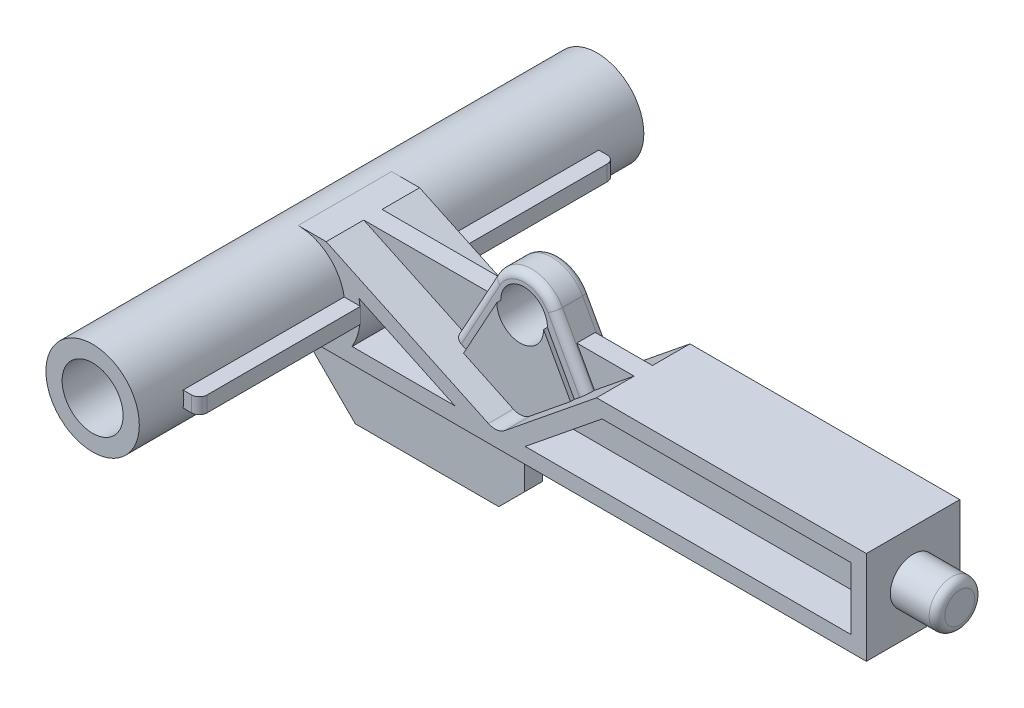
SolidWorks part; units mm, degrees
ref_plane "Front Plane" through (0, 0, 0) normal (0, 0, 1) x (1, 0, 0)
ref_plane "Top Plane" through (0, 0, 0) normal (0, 1, 0) x (1, 0, 0)
ref_plane "Right Plane" through (0, 0, 0) normal (1, 0, 0) x (0, 0, -1)
sketch "Sketch1" plane through (0, 0, 0) normal (0, 0, 1) x (1, 0, 0)
  line L0 (0, 0) -> (36.5, 0)
  line L1 (36.5, 0) -> (36.5, 6)
  line L2 (36.5, 6) -> (20.75, 6)
  line L3 (20.75, 6) -> (11.75, 6) construction
  line L4 (20.75, 6) -> (20.75, 2) construction
  line L5 (20.75, 2) -> (11.75, 2) construction
  line L6 (11.75, 2) -> (11.75, 6) construction
  line L7 (16.75, 10) -> (16.75, 2) construction
  line L8 (12.75, 6) -> (20.75, 6) construction
  line L9 (15.5737, 2.9411) -> (11.75, 6)
  line L10 (11.75, 6) -> (0, 6)
  line L11 (0, 6) -> (0, 0) construction
  arc A1 (20.75, 6) -> (19.541, 3.1347) centre (16.75, 6) cw
  arc A2 (15.5737, 2.9411) -> (19.541, 3.1347) centre (17.4478, 5.2837) ccw
  circle A4 centre (0, 3) radius 3
  dimension "D4" = 3
  dimension "D1" = 36.5
  dimension "D2" = 6
  dimension "D3" = 15.75
  dimension "D5" = 4
  dimension "D6" = 9
extrude "Boss-Extrude3" add sketch "Sketch1" along normal mid plane 6 contours A4 L0 L1 L2 A1 A2 L9 L10 region at (19.7193, 2.8172, 0)
sketch "Sketch2" plane through (0, 0, 0) normal (0, 0, 1) x (1, 0, 0)
  circle A0 centre (0, 3) radius 3
extrude "Boss-Extrude4" add sketch "Sketch2" along normal mid plane 32.41
sketch "Sketch5" plane through (0, 0, 16.205) normal (0, 0, 1) x (1, 0, 0)
  circle A0 centre (0, 3) radius 1.96
  dimension "D1" = 3.92
extrude "Cut-Extrude2" cut sketch "Sketch5" against normal blind 32.8
sketch "Sketch6" plane through (36.5, 0, 0) normal (1, 0, 0) x (0, 0, -1)
  circle A0 centre (0, 3) radius 1.465
  dimension "D1" = 2.93
extrude "Boss-Extrude7" add sketch "Sketch6" along normal blind 3 contours A0
fillet "Fillet1" radius 0.5 1 edges at (39.5, 3, -1.465)
sketch "Sketch12" plane through (0, 0, 0) normal (0, 0, 1) x (1, 0, 0)
  line L0 (36.5, 0) -> (12.12, 0) construction
  line L1 (0, 0) -> (36.5, 0) construction
  line L2 (12.12, 0) -> (12.12, -3.97)
  line L3 (12.12, -3.97) -> (10.4795, -5.6105)
  line L4 (10.4795, -5.6105) -> (1.2595, -5.6105)
  line L5 (1.2595, -5.6105) -> (-2.8064, -1.5446)
  line L6 (-2.8064, -1.5446) -> (-2.8064, 1.9396)
  line L7 (12.12, 0) -> (0, 0)
  circle A0 centre (0, 3) radius 3 construction
  arc A1 (-2.8064, 1.9396) -> (0, 0) centre (0, 3) ccw
  dimension "D1" = 24.38
  dimension "D2" = 3.97
  dimension "D3" = 2.32
  dimension "D4" = 9.22
  dimension "D5" = 5.75
extrude "Boss-Extrude8" add sketch "Sketch12" along normal mid plane 1.18
sketch "Sketch14" plane through (0, 0, 0) normal (0, 0, 1) x (1, 0, 0)
  line L1 (4, 2.5) -> (4, 3.5)
  line L2 (4, 3.5) -> (2.958, 3.5)
  line L3 (4, 2.5) -> (2.958, 2.5)
  circle A0 centre (0, 3) radius 3 construction
  arc A2 (2.958, 3.5) -> (2.958, 2.5) centre (0, 3) cw
  point P6 (4, 3)
  dimension "D1" = 1
extrude "Boss-Extrude9" add sketch "Sketch14" along normal mid plane 26.7
fillet "Fillet7" radius 0.5 1 edges at (4, 3, 13.35)
fillet "Fillet8" radius 0.5 1 edges at (4, 3, -13.35)
sketch "Sketch15" plane through (0, 0, 0) normal (0, 0, 1) x (1, 0, 0)
  line L0 (5.875, 6) -> (27.0772, 6)
  line L1 (11.75, 6) -> (0, 6) construction
  line L2 (36.5, 6) -> (20.75, 6) construction
  line L3 (27.0772, 6) -> (27.0772, 1.4897)
  line L4 (27.0772, 1.4897) -> (5.875, 1.4897)
  line L5 (5.875, 1.4897) -> (5.875, 6)
extrude "Boss-Extrude10" add sketch "Sketch15" along normal mid plane 6
sketch "Sketch16" plane through (0, 0, 0) normal (0, 0, 1) x (1, 0, 0)
  line L0 (0, 6) -> (1.8, 6)
  line L1 (36.5, 6) -> (0, 6) construction
  line L2 (1.8, 6) -> (19.17, 6) construction
  line L3 (1.8, 6) -> (19.17, 6)
  line L5 (1.8, 6) -> (12.2149, 1.0953)
  line L6 (13.2702, 1.2228) -> (19.17, 6)
  arc A0 (13.2702, 1.2228) -> (12.2149, 1.0953) centre (12.6409, 2) cw
  dimension "D4" = 1
  dimension "D1" = 1.8
  dimension "D2" = 17.37
extrude "Cut-Extrude4" cut sketch "Sketch16" against normal mid plane 6 contours A0 L6 L3 L5 region at (11.2486, 4.2809, 0)
sketch "Sketch17" plane through (0, 0, 0) normal (0, 0, 1) x (1, 0, 0)
  line L0 (1.8, 6) -> (19.17, 6)
  line L1 (19.17, 6) -> (19.17, 0.4969)
  line L2 (19.17, 0.4969) -> (1.8, 0.4969)
  line L3 (1.8, 0.4969) -> (4.8905, 2.3962)
  line L4 (4.8905, 2.3962) -> (1.8, 6)
extrude "Boss-Extrude11" add sketch "Sketch17" along normal mid plane 1.18
sketch "Sketch19" plane through (0, 0, 0) normal (0, 0, 1) x (1, 0, 0)
  line L0 (12.6557, 1.0001) -> (12.6557, 11.1504) construction
  line L1 (12.6557, 6.0753) -> (12.6557, 8.6853)
  line L2 (1.8, 6) -> (8.17, 3.0002) construction
  line L3 (1.8, 6) -> (12.2149, 1.0953) construction
  line L4 (8.17, 3.0002) -> (10.6847, 7.5691)
  line L5 (14.6269, 7.5692) -> (15.4907, 6)
  line L6 (19.17, 6) -> (1.8, 6) construction
  line L7 (15.4907, 6) -> (16.625, 3.9393)
  line L8 (13.2702, 1.2228) -> (19.17, 6) construction
  line L9 (8.17, 3.0002) -> (12.2149, 1.0953)
  line L10 (16.625, 3.9393) -> (13.2702, 1.2228)
  arc A0 (12.2149, 1.0953) -> (13.2702, 1.2228) centre (12.6409, 2) ccw construction
  arc A1 (12.2149, 1.0953) -> (13.2702, 1.2228) centre (12.6409, 2) ccw construction
  arc A2 (12.2149, 1.0953) -> (13.2702, 1.2228) centre (12.6409, 2) ccw
  arc A3 (10.6847, 7.5691) -> (14.6269, 7.5692) centre (12.6558, 6.4842) cw
  dimension "D5" = 2.25
  dimension "D1" = 2.61
  dimension "D2" = 6.37
  dimension "D3" = 151.173
  dimension "D4" = 151.17
extrude "Boss-Extrude12" add sketch "Sketch19" along normal mid plane 2.79 contours A2 L10 L7 L5 A3 L4 L9
sketch "Sketch20" plane through (0, 0, 1.395) normal (0, 0, 1) x (1, 0, 0)
  line L0 (11.1558, 6.4842) -> (9.0184, 2.6006)
  line L1 (8.17, 3.0002) -> (12.2149, 1.0953) construction
  line L2 (8.17, 3.0002) -> (10.6847, 7.5691) construction
  line L3 (14.1558, 6.4842) -> (15.886, 3.3409)
  line L4 (16.625, 3.9393) -> (13.2702, 1.2228) construction
  line L5 (14.6269, 7.5692) -> (16.625, 3.9393) construction
  line L6 (8.17, 3.0002) -> (9.0184, 2.6006)
  line L7 (15.886, 3.3409) -> (16.625, 3.9393)
  line L8 (14.6269, 7.5692) -> (16.625, 3.9393)
  arc A2 (10.6847, 7.5691) -> (14.6269, 7.5692) centre (12.6558, 6.4842) cw
  arc A3 (11.1558, 6.4842) -> (14.1558, 6.4842) centre (12.6558, 6.4842) ccw
  circle A4 centre (12.6558, 6.4842) radius 1.5
  dimension "D1" = 3
extrude "Cut-Extrude6" cut sketch "Sketch20" against normal mid plane 41.79 contours A3 A4 region at (12.6558, 6.4842, 1.395)
sketch "Sketch21" plane through (0, 0, 1.395) normal (0, 0, 1) x (1, 0, 0)
  line L0 (11.1558, 6.4842) -> (9.0184, 2.6006)
  line L1 (1.8, 6) -> (12.2149, 1.0953) construction
  line L2 (8.17, 3.0002) -> (9.821, 6) construction
  line L3 (14.1558, 6.4842) -> (15.886, 3.3409)
  line L4 (16.625, 3.9393) -> (13.2702, 1.2228) construction
  line L5 (15.4907, 6) -> (16.625, 3.9393) construction
  line L6 (8.17, 3.0002) -> (9.0184, 2.6006)
  line L7 (16.625, 3.9393) -> (15.886, 3.3409)
  line L8 (10.6847, 7.5691) -> (8.17, 3.0002)
  line L9 (14.6269, 7.5692) -> (16.625, 3.9393)
  circle A0 centre (12.6558, 6.4842) radius 1.5 construction
  arc A1 (10.6847, 7.5691) -> (14.6269, 7.5692) centre (12.6558, 6.4842) cw
  arc A2 (11.1558, 6.4842) -> (14.1558, 6.4842) centre (12.6558, 6.4842) ccw
extrude "Cut-Extrude7" cut sketch "Sketch21" against normal mid plane 0.5
sketch "Sketch22" plane through (0, 0, -1.395) normal (0, 0, -1) x (-1, 0, 0)
  line L0 (-14.1558, 6.4842) -> (-15.886, 3.3409)
  line L1 (-13.2702, 1.2228) -> (-19.17, 6) construction
  line L2 (-15.4907, 6) -> (-16.625, 3.9393) construction
  line L3 (-11.1558, 6.4842) -> (-9.0184, 2.6006)
  line L4 (-8.17, 3.0002) -> (-12.2149, 1.0953) construction
  line L5 (-8.17, 3.0002) -> (-10.6847, 7.5691) construction
  line L6 (-16.625, 3.9393) -> (-15.886, 3.3409)
  line L7 (-8.17, 3.0002) -> (-9.0184, 2.6006)
  line L8 (-14.6269, 7.5692) -> (-16.625, 3.9393)
  line L9 (-10.6847, 7.5691) -> (-8.17, 3.0002)
  circle A0 centre (-12.6558, 6.4842) radius 1.5 construction
  arc A1 (-14.6269, 7.5692) -> (-10.6847, 7.5691) centre (-12.6558, 6.4842) cw
  arc A2 (-14.1558, 6.4842) -> (-11.1558, 6.4842) centre (-12.6558, 6.4842) ccw
extrude "Cut-Extrude8" cut sketch "Sketch22" against normal mid plane 0.5
fillet "Fillet9" radius 0.5 3 edges at (9.4273, 5.2846, -1.145) (15.626, 5.7542, -1.145) (12.6558, 8.7342, -1.145)
fillet "Fillet10" radius 0.5 3 edges at (15.626, 5.7542, 1.145) (9.4273, 5.2846, 1.145) (12.6558, 8.7342, 1.145)
sketch "Sketch23" plane through (0, 0, -3) normal (0, 0, -1) x (-1, 0, 0)
  line L0 (-35.5, 5) -> (-35.5, 1)
  line L1 (-35.5, 1) -> (-14.23, 1)
  line L2 (-36.5, 0) -> (-36.5, 6) construction
  line L5 (-35.5, 5) -> (-19.17, 5)
  line L6 (-36.5, 6) -> (-19.17, 6) construction
  line L7 (-19.17, 5) -> (-14.23, 1)
  line L8 (-15.886, 3.3409) -> (-13.2702, 1.2228) construction
  dimension "D1" = 1
  dimension "D3" = 1
extrude "Cut-Extrude9" cut sketch "Sketch23" against normal blind 2.5
sketch "Sketch24" plane through (0, 0, -3) normal (0, 0, -1) x (-1, 0, 0)
  line L0 (-10.0701, 1) -> (-3.4641, 1)
  line L1 (-3.8956, 3.9078) -> (-10.0701, 1)
  line L2 (-9.0184, 2.6006) -> (-12.2149, 1.0953) construction
  line L3 (-1.8, 6) -> (-12.2149, 1.0953) construction
  arc A0 (-3.4641, 1) -> (-3.8956, 3.9078) centre (0, 3) cw
  arc A1 (-2.958, 2.5) -> (0, 0) centre (0, 3) ccw construction
  dimension "D2" = 1
  dimension "D1" = 1
extrude "Cut-Extrude10" cut sketch "Sketch24" against normal blind 2.5
sketch "Sketch25" plane through (0, 0, 3) normal (0, 0, 1) x (1, 0, 0)
  line L2 (19.5241, 5) -> (35.5, 5)
  line L3 (35.5, 5) -> (35.5, 1)
  line L5 (36.5, 6) -> (19.17, 6) construction
  line L6 (36.5, 0) -> (36.5, 6) construction
  line L16 (35.5, 1) -> (14.5841, 1)
  line L17 (0, 0) -> (36.5, 0) construction
  line L18 (19.5241, 5) -> (14.5841, 1)
  dimension "D1" = 1
  dimension "D2" = 1
  dimension "D4" = 1
sketch "Sketch26" plane through (0, 0, 3) normal (0, 0, 1) x (1, 0, 0)
  line L0 (3.4641, 1) -> (10.0701, 1)
  line L1 (0, 0) -> (36.5, 0) construction
  line L2 (1.8, 6) -> (12.2149, 1.0953) construction
  line L3 (3.8956, 3.9078) -> (10.0701, 1)
  arc A0 (3.8956, 3.9078) -> (3.4641, 1) centre (0, 3) cw
  circle A1 centre (0, 3) radius 3 construction
  arc A2 (0, 0) -> (2.958, 2.5) centre (0, 3) ccw construction
  dimension "D1" = 1
  dimension "D6" = 1
  dimension "D2" = 1
  dimension "D3" = 1
  dimension "D4" = 1
extrude "Cut-Extrude12" cut sketch "Sketch25" against normal blind 2.5
extrude "Cut-Extrude14" cut sketch "Sketch26" against normal blind 2.5
